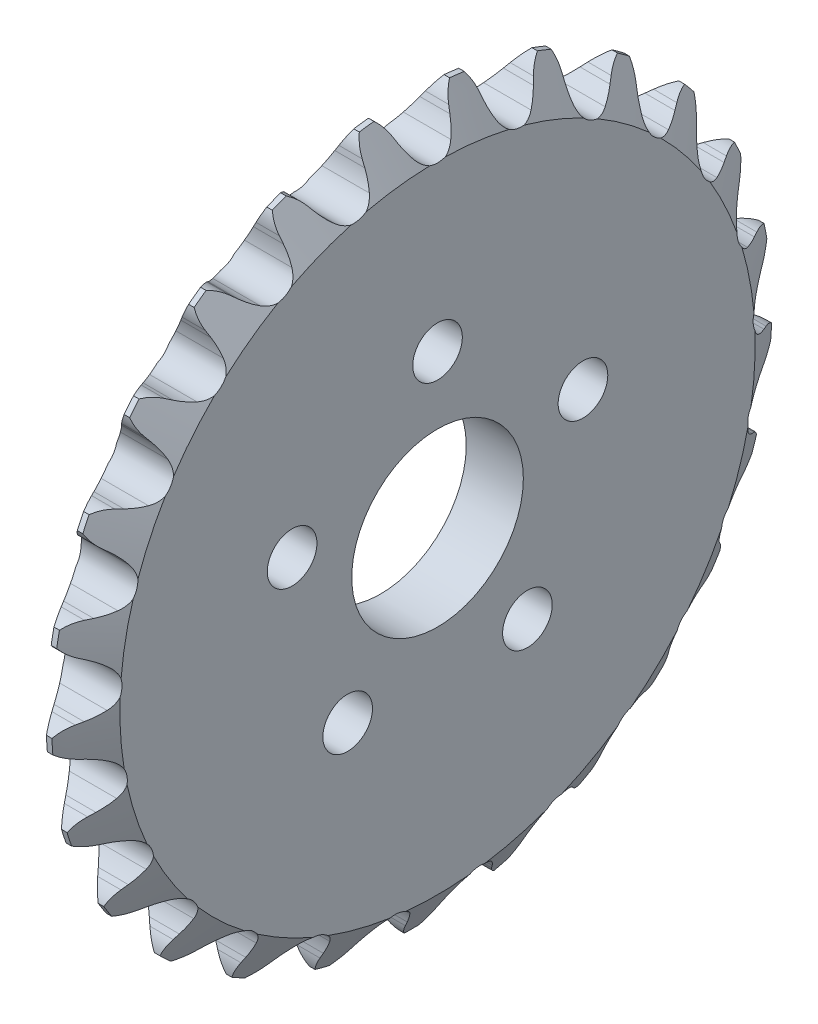
SolidWorks part; units mm, degrees
material "Alloy Steel"
ref_plane "Front Plane" through (0, 0, 0) normal (0, 0, 1) x (1, 0, 0)
ref_plane "Top Plane" through (0, 0, 0) normal (0, 1, 0) x (1, 0, 0)
ref_plane "Right Plane" through (0, 0, 0) normal (1, 0, 0) x (0, 0, -1)
ref_axis "X AXIS" through (-88.99, 0, 0) along (1, 0, 0)
ref_axis "Y AXIS" through (0, -55, 0) along (0, 1, 0)
ref_axis "Z AXIS" through (0, 0, 55) along (0, 0, -1)
other "Freeze***"
sketch "Sketch1" plane through (0, 0, 0) normal (1, 0, 0) x (0, 0, -1)
  line L0 (0, 25.3325) -> (-6.2999, 24.5366) construction
  line L1 (-1.9346, 25.3368) -> (-2.0951, 25.7414)
  line L2 (-1.9346, 25.3368) -> (2.0985, 26.9369) construction
  line L3 (2.0985, 26.9369) -> (0, 25.3325) construction
  line L4 (0, 25.3325) -> (-1.9329, 25.3325) construction
  line L5 (-3.4326, 27.1722) -> (-3.15, 24.9345) construction
  line L6 (0, 25.3325) -> (0, 23.6351) construction
  circle A0 centre (0, 0) radius 25.3325 construction
  arc A1 (-1.3484, 24.3015) -> (0, 23.6351) centre (0, 25.3325) ccw
  arc A2 (-1.3484, 24.3015) -> (-1.9346, 25.3368) centre (2.0985, 26.9369) cw
  arc A3 (-2.0951, 25.7414) -> (-3.4326, 27.1722) centre (-4.5863, 24.7531) ccw
sketch "Sketch2" plane through (0, 0, 0) normal (0, 0, 1) x (1, 0, 0)
  line L0 (0, 0) -> (0, 26.92) construction
  line L1 (-0.2064, 26.92) -> (0.2064, 26.92)
  line L2 (0.2064, 26.92) -> (2.1336, 23.745)
  line L3 (2.1336, 23.745) -> (2.1336, 0)
  line L4 (-2.1336, 0) -> (2.1336, 0)
  line L5 (-2.1336, 23.745) -> (-2.1336, 0)
  line L6 (-0.2064, 26.92) -> (-2.1336, 23.745)
  dimension "D1" = 26.92
  dimension "D2" = 4.2672
revolve "Revolve1" add sketch "Sketch2" angle 360 about L4
sketch "Sketch3" plane through (0, 0, 0) normal (1, 0, 0) x (0, 0, -1)
  line L0 (-1.9346, 25.3368) -> (-2.0951, 25.7414) construction
  line L1 (-1.9346, 25.3368) -> (-2.0951, 25.7414)
  line L2 (0, 23.6351) -> (0, 0) construction
  line L3 (1.9346, 25.3368) -> (2.0951, 25.7414)
  arc A0 (-2.0951, 25.7414) -> (-3.4326, 27.1722) centre (-4.5863, 24.7531) ccw construction
  arc A1 (-1.9346, 25.3368) -> (-1.3484, 24.3015) centre (2.0985, 26.9369) ccw construction
  arc A2 (-1.3484, 24.3015) -> (0, 23.6351) centre (0, 25.3325) ccw construction
  arc A3 (-2.0951, 25.7414) -> (-3.4326, 27.1722) centre (-4.5863, 24.7531) ccw
  arc A4 (-1.9346, 25.3368) -> (-1.3484, 24.3015) centre (2.0985, 26.9369) ccw
  arc A5 (-1.3484, 24.3015) -> (1.3484, 24.3015) centre (0, 25.3325) ccw
  arc A6 (1.9346, 25.3368) -> (1.3484, 24.3015) centre (-2.0985, 26.9369) cw
  arc A7 (2.0951, 25.7414) -> (3.4326, 27.1722) centre (4.5863, 24.7531) cw
  arc A8 (-3.4326, 27.1722) -> (3.4326, 27.1722) centre (0, 0) cw
extrude "Cut-Extrude1" cut sketch "Sketch3" against normal through all both and the other way through all contours A8 A3 L1 A4 A5 A6 L3 A7 region at (0, 25.8551, 0)
pattern_circular "CirPattern1" count 25 over 360 about axis through (-88.99, 0, 0) along (1, 0, 0) of "Cut-Extrude1"
sketch "Sketch4" plane through (2.1336, 0, 0) normal (1, 0, 0) x (0, 0, -1)
  line L0 (0, 0) -> (0, 11.43) construction
  circle A0 centre (0, 0) radius 6.4135
  circle A1 centre (0, 11.43) radius 1.8542
  circle A2 centre (10.8706, 3.5321) radius 1.8542
  circle A3 centre (6.7184, -9.2471) radius 1.8542
  circle A4 centre (-6.7184, -9.2471) radius 1.8542
  circle A5 centre (-10.8706, 3.5321) radius 1.8542
  point P15 (0, 0)
  dimension "D1" = 12.827
  dimension "D2" = 5
  dimension "D3" = 3.7084
  dimension "D4" = 11.43
extrude "Cut-Extrude2" cut sketch "Sketch4" against normal through all
sketch "Sketch5" plane through (-2.1336, 0, 0) normal (-1, 0, 0) x (0, 0, 1)
  circle A0 centre (0, 0) radius 23.7837
equation "\"p\" = 2 / 8"
equation "\"n\" = 25"
equation "\"Dr\"= 0.13"
equation "\"Ds\"= 1.005 * \"Dr\" + 0.003"
equation "\"PD\"= \"p\" * cosec ( 180 / \"n\" )"
equation "\"A\"= 35 + 60 / \"n\""
equation "\"B\"= 18 - 56 / \"n\""
equation "\"ac\"= 0.8 * \"Dr\""
equation "\"ab\"= 1.4 * \"Dr\""
equation "\"D1@Sketch1\"=\"PD\""
equation "\"D2@Sketch1\"=\"p\""
equation "\"D3@Sketch1\"=\"Ds\""
equation "\"D4@Sketch1\"=\"A\""
equation "\"D5@Sketch1\"=\"B\""
equation "\"D6@Sketch1\"=\"ac\""
equation "\"D7@Sketch1\"=\"ab\""
equation "\"D1@Sketch2\"=(\"PD\"+\"p\"/2)/2"
equation "\"D4@Sketch2\"=\"p\"/2"
equation "\"D1@CirPattern1\"=\"n\""
